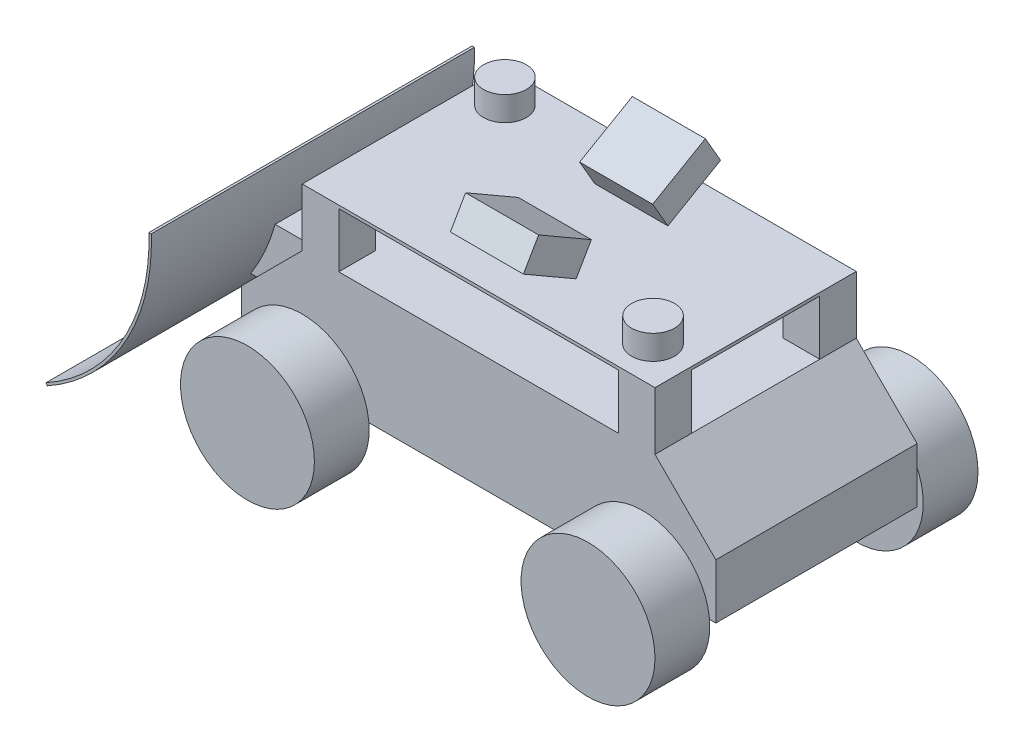
SolidWorks part; units mm, degrees
ref_plane "Front Plane" through (0, 0, 0) normal (0, 0, 1) x (1, 0, 0)
ref_plane "Top Plane" through (0, 0, 0) normal (0, 1, 0) x (1, 0, 0)
ref_plane "Right Plane" through (0, 0, 0) normal (1, 0, 0) x (0, 0, -1)
sketch "Sketch1" plane through (0, 0, 0) normal (0, 1, 0) x (1, 0, 0)
  line L1 (-495, 210) -> (495, 210)
  line L2 (-495, 210) -> (-495, -210)
  line L3 (-495, -210) -> (495, -210)
  line L4 (495, 210) -> (495, -210)
  line L5 (-495, 210) -> (495, -210) construction
  line L6 (-495, -210) -> (495, 210) construction
  point P0 (0, 0)
  dimension "D1" = 420
  dimension "D2" = 990
extrude "Boss-Extrude1" add sketch "Sketch1" along normal blind 241.3
sketch "Sketch2" plane through (0, 0, 210) normal (0, 0, 1) x (1, 0, 0)
  line L0 (-495, 0) -> (495, 0) construction
  line L1 (-355.3, 0) -> (0, 0) construction
  line L2 (0, 0) -> (355.3, 0) construction
  line L3 (-495, 241.3) -> (-495, 0) construction
  circle A0 centre (-355.3, 0) radius 139.7
  circle A1 centre (355.3, 0) radius 139.7
  dimension "D1" = 279.4
extrude "Boss-Extrude2" add sketch "Sketch2" along normal blind 114.3 from offset 12.7 separate body
mirror "Mirror2" about plane through (0, 0, 0) normal (0, 0, 1) of bodies 103 102
sketch "Sketch3" plane through (0, 0, 337) normal (0, 0, 1) x (1, 0, 0)
  circle A0 centre (-355.3, 0) radius 25.4
  circle A1 centre (355.3, 0) radius 25.4
  dimension "D1" = 50.8
extrude "Boss-Extrude3" add sketch "Sketch3" against normal up to surface (674 mm away) up to face at (495, 0, -337)
chamfer "Chamfer1" distance 127 angle 45 2 edges at (495, 241.3, 0) (-495, 241.3, 0)
sketch "Sketch4" plane through (0, 0, 210) normal (0, 0, 1) x (1, 0, 0)
  line L1 (-368, 241.3) -> (368, 241.3) construction
  line L2 (355.3, -139.7) -> (-355.3, -139.7) construction
  line L3 (-495, 114.3) -> (-495, 0) construction
  arc A0 (-558.5, 241.3) -> (-774.4, -139.7) centre (-977.3553, 226.9797) cw
  circle A3 centre (-355.3, 0) radius 139.7 construction
  point P7 (0, 0)
  point P10 (-534.9962, 241.3)
  point P11 (-772.6559, -139.7)
  point P12 (-561.1701, 241.3)
  dimension "D1" = 279.4
  dimension "D3" = 419.1
  dimension "D2" = 63.5
extrude "Extrude-Thin1" add sketch "Sketch4" along normal up to surface and the other way up to surface separate body thin up to face at (-215.6, 0, 337) other way up to face at (-215.6, 0, -337) thin type mid plane wall 5.08
sketch "Sketch5" plane through (-495, 0, 0) normal (-1, 0, 0) x (0, 0, 1)
  line L0 (210, 114.3) -> (-210, 114.3) construction
  line L1 (-63.5, 114.3) -> (63.5, 114.3)
  line L2 (-63.5, 114.3) -> (-63.5, 0)
  line L3 (-63.5, 0) -> (63.5, 0)
  line L4 (63.5, 114.3) -> (63.5, 0)
  line L5 (-210, 0) -> (210, 0) construction
  point P8 (0, 0)
  dimension "D1" = 127
extrude "Boss-Extrude4" add sketch "Sketch5" along normal up to surface (76.0505 mm away) up to face at (-637.5424, 34.419, 0)
sketch "Sketch6" plane through (0, 241.3, 0) normal (0, 1, 0) x (1, 0, 0)
  line L1 (-368, 210) -> (-291.8, 210)
  line L2 (-368, 210) -> (-368, 133.8)
  line L3 (-368, 133.8) -> (-291.8, 133.8)
  line L4 (-291.8, 210) -> (-291.8, 133.8)
  line L5 (-368, -210) -> (-291.8, -210)
  line L6 (-368, -210) -> (-368, -133.8)
  line L7 (-368, -133.8) -> (-291.8, -133.8)
  line L8 (-291.8, -210) -> (-291.8, -133.8)
  line L9 (368, 210) -> (291.8, 210)
  line L10 (368, 210) -> (368, 133.8)
  line L11 (368, 133.8) -> (291.8, 133.8)
  line L12 (291.8, 210) -> (291.8, 133.8)
  line L13 (368, -210) -> (291.8, -210)
  line L14 (368, -210) -> (368, -133.8)
  line L15 (368, -133.8) -> (291.8, -133.8)
  line L16 (291.8, -210) -> (291.8, -133.8)
  dimension "D1" = 76.2
extrude "Boss-Extrude5" add sketch "Sketch6" along normal blind 114.3
sketch "Sketch7" plane through (0, 355.6, 0) normal (0, 1, 0) x (1, 0, 0)
  line L1 (-368, 210) -> (368, 210)
  line L2 (-368, 210) -> (-368, -210)
  line L3 (-368, -210) -> (368, -210)
  line L4 (368, 210) -> (368, -210)
extrude "Boss-Extrude6" add sketch "Sketch7" along normal blind 6.35
sketch "Sketch8" plane through (0, 361.95, 0) normal (0, 1, 0) x (1, 0, 0)
  circle A0 centre (-298.8758, 143.7797) radius 44.7486
  circle A1 centre (286.9928, -133.0298) radius 44.7486
extrude "Boss-Extrude7" add sketch "Sketch8" along normal blind 50.8
sketch "Sketch9" plane through (-368, 0, 0) normal (-1, 0, 0) x (0, 0, 1)
  line L0 (-205.6852, 425.45) -> (-173.9352, 480.4426)
  line L1 (-173.9352, 480.4426) -> (-63.95, 416.9426)
  line L2 (-63.95, 416.9426) -> (-95.7, 361.95)
  line L3 (-95.7, 361.95) -> (-205.6852, 425.45)
  line L5 (-210, 361.95) -> (210, 361.95) construction
  line L6 (0, 0) -> (0, 812.28) construction
  line L7 (63.95, 416.9426) -> (95.7, 361.95)
  line L8 (173.9352, 480.4426) -> (63.95, 416.9426)
  line L9 (205.6852, 425.45) -> (173.9352, 480.4426)
  line L10 (95.7, 361.95) -> (205.6852, 425.45)
  dimension "D1" = 127
  dimension "D2" = 63.5
  dimension "D3" = 114.3
  dimension "D4" = 30
extrude "Boss-Extrude8" add sketch "Sketch9" against normal blind 152.4 from offset 304.8 separate body offset against normal yes
sketch "Sketch10" plane through (0, 361.95, 0) normal (0, 1, 0) x (1, 0, 0)
  circle A0 centre (-308.2819, -151.8421) radius 54.5662
  circle A1 centre (286.9928, 135.7173) radius 68.4382
extrude "Boss-Extrude9" [suppressed] add sketch "Sketch10" along normal blind 609.6
